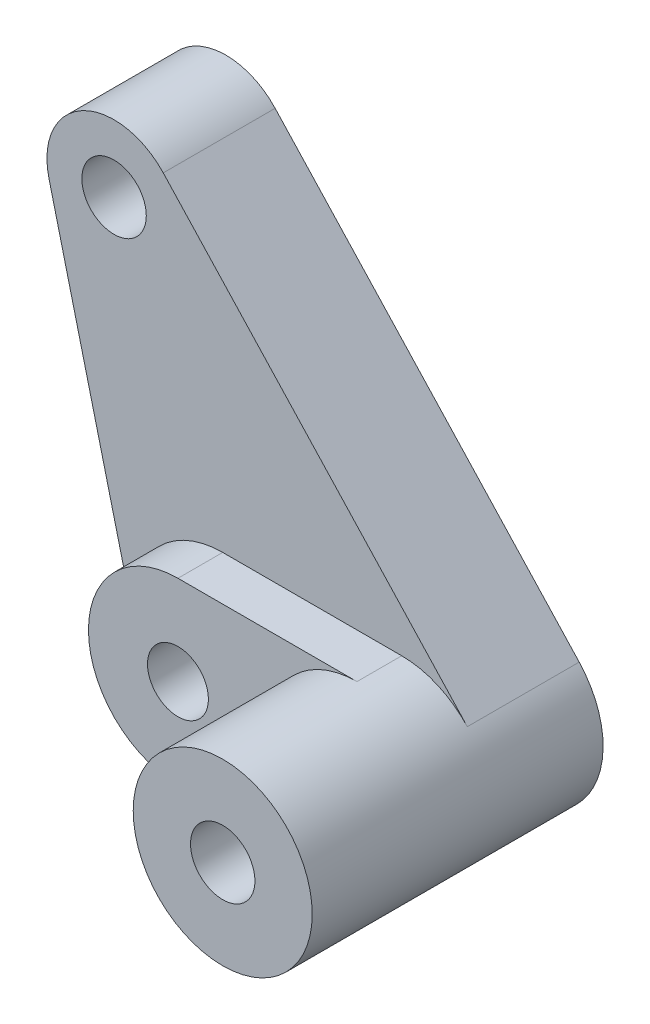
SolidWorks part; units mm, degrees
ref_plane "Front Plane" through (0, 0, 0) normal (0, 0, 1) x (1, 0, 0)
ref_plane "Top Plane" through (0, 0, 0) normal (0, 1, 0) x (1, 0, 0)
ref_plane "Right Plane" through (0, 0, 0) normal (1, 0, 0) x (0, 0, -1)
sketch "Sketch1" plane through (0, 0, 0) normal (0, 0, 1) x (1, 0, 0)
  line L0 (-12.7, 0) -> (0, 0) construction
  line L1 (0, -6.35) -> (-12.7, -6.35)
  line L3 (-20.4085, 24.3219) -> (0, 0) construction
  line L5 (4.6542, 4.3198) -> (-16.9178, 27.5618)
  line L6 (-25.0292, 23.1683) -> (-18.8609, -1.5381)
  line L7 (0, 0) -> (-20.4085, 24.3219) construction
  arc A0 (0, -6.35) -> (4.6542, 4.3198) centre (0, 0) ccw
  arc A1 (-18.8609, -1.5381) -> (-12.7, -6.35) centre (-12.7, 0) ccw
  arc A3 (-16.9178, 27.5618) -> (-25.0292, 23.1683) centre (-20.4085, 24.3219) ccw
  circle A4 centre (-12.7, 0) radius 2.159
  circle A5 centre (-20.4085, 24.3219) radius 2.286
  circle A6 centre (0, 0) radius 2.286
  dimension "D3" = 4.318
  dimension "D4" = 9.525
  dimension "D5" = 12.7
  dimension "D6" = 6.35
  dimension "D8" = 4.572
  dimension "D9" = 4.572
  dimension "D1" = 12.7
  dimension "D2" = 31.75
  dimension "D7" = 50
extrude "Boss-Extrude1" add sketch "Sketch1" along normal mid plane 7.9375
sketch "Sketch3" plane through (0, 0, 3.9688) normal (0, 0, 1) x (1, 0, 0)
  circle A0 centre (0, 0) radius 6.35
  circle A1 centre (0, 0) radius 2.286 construction
  circle A2 centre (0, 0) radius 2.286
  arc A3 (0, -6.35) -> (4.6542, 4.3198) centre (0, 0) ccw construction
extrude "Boss-Extrude2" add sketch "Sketch3" along normal blind 12.7
sketch "Sketch4" plane through (0, 0, -3.9688) normal (0, 0, -1) x (-1, 0, 0)
  line L1 (12.7, 5.1326) -> (8.255, 2.5663)
  line L2 (8.255, 2.5663) -> (8.255, -2.5663)
  line L3 (8.255, -2.5663) -> (12.7, -5.1326)
  line L4 (12.7, -5.1326) -> (17.145, -2.5663)
  line L5 (17.145, -2.5663) -> (17.145, 2.5663)
  line L6 (17.145, 2.5663) -> (12.7, 5.1326)
  circle A0 centre (12.7, 0) radius 4.445 construction
  dimension "D1" = 8.89
extrude "Cut-Extrude1" cut sketch "Sketch4" against normal blind 3.175
sketch "Sketch5" plane through (0, 0, 3.9688) normal (0, 0, 1) x (1, 0, 0)
  line L0 (-12.7, 6.35) -> (0, 6.35)
  line L1 (-12.7, -6.35) -> (0, -6.35) construction
  line L2 (-12.7, -6.35) -> (0, -6.35)
  arc A0 (-12.7, 6.35) -> (-12.7, -6.35) centre (-12.7, 0) ccw
  circle A1 centre (0, 0) radius 6.35 construction
  arc A2 (0, 6.35) -> (0, -6.35) centre (0, 0) ccw
  arc A3 (-18.8609, -1.5381) -> (-12.7, -6.35) centre (-12.7, 0) ccw construction
  circle A4 centre (-12.7, 0) radius 2.159 construction
  circle A5 centre (-12.7, 0) radius 2.159
extrude "Boss-Extrude3" add sketch "Sketch5" along normal blind 3.175
